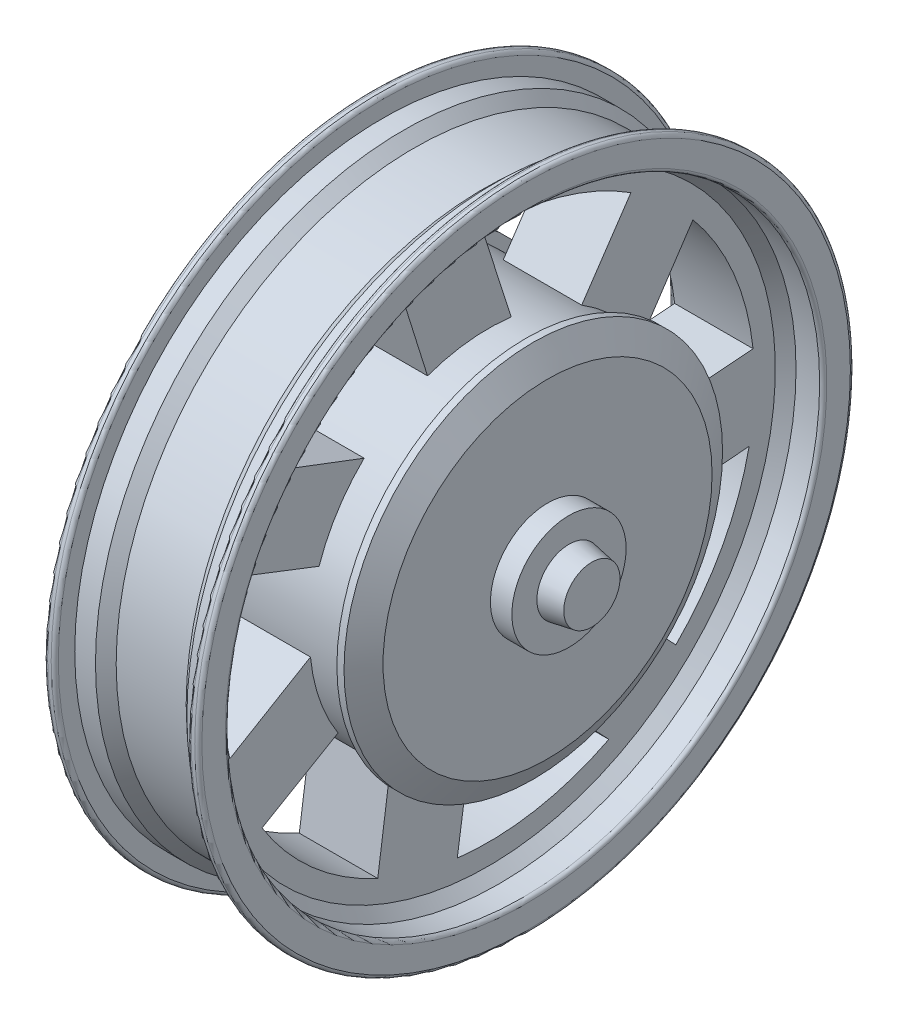
SolidWorks part; units mm, degrees
ref_plane "Front Plane" through (0, 0, 0) normal (0, 0, 1) x (1, 0, 0)
ref_plane "Top Plane" through (0, 0, 0) normal (0, 1, 0) x (1, 0, 0)
ref_plane "Right Plane" through (0, 0, 0) normal (1, 0, 0) x (0, 0, -1)
sketch "Sketch4" plane through (0, 0, 0) normal (0, 0, 1) x (1, 0, 0)
  line L0 (0, 0) -> (0, 201) construction
  line L2 (27.4562, 201) -> (34.9562, 208)
  line L3 (34.9562, 208) -> (54, 208)
  line L4 (54, 208) -> (54, 229.5)
  line L5 (54, 229.5) -> (46.5, 229.5)
  line L6 (46.5, 229.5) -> (46.5, 215.5)
  line L7 (46.5, 215.5) -> (32, 215.5)
  line L8 (32, 215.5) -> (24.5, 208.5)
  line L9 (24.5, 208.5) -> (-24.5, 208.5)
  line L10 (-54, 229.5) -> (-46.5, 229.5)
  line L11 (-54, 208) -> (-54, 229.5)
  line L12 (-46.5, 229.5) -> (-46.5, 215.5)
  line L13 (-34.9562, 208) -> (-54, 208)
  line L14 (-46.5, 215.5) -> (-32, 215.5)
  line L15 (-27.4562, 201) -> (-34.9562, 208)
  line L16 (-32, 215.5) -> (-24.5, 208.5)
  line L17 (-130.2898, 0) -> (128.111, 0) construction
  line L18 (-27.4562, 201) -> (-27.4562, 0)
  line L19 (-27.4562, 0) -> (27.4562, 0)
  line L20 (27.4562, 0) -> (27.4562, 201)
  point P23 (0, 208.5)
  dimension "D1" = 14.5
  dimension "D2" = 215.5
  dimension "D4" = 7.5
  dimension "D5" = 7.5
  dimension "D6" = 7.5
  dimension "D7" = 7.5
  dimension "D8" = 54
  dimension "D9" = 54.9124
  dimension "D10" = 229.5
revolve "Revolve1" add sketch "Sketch4" angle 360 about L17
sketch "Sketch5" plane through (27.4562, 0, 0) normal (1, 0, 0) x (0, 0, -1)
  circle A0 centre (0, 0) radius 125
  dimension "D1" = 250
extrude "Boss-Extrude2" add sketch "Sketch5" along normal up to surface (26.5438 mm away) up to face at (54, 0, 229.5)
sketch "Sketch6" plane through (-27.4562, 0, 0) normal (-1, 0, 0) x (0, 0, 1)
  circle A0 centre (0, 0) radius 125
  dimension "D1" = 250
extrude "Boss-Extrude3" add sketch "Sketch6" along normal up to surface (26.5438 mm away) up to face at (-54, 0, 208)
sketch "Sketch7" plane through (-27.4562, 0, 0) normal (-1, 0, 0) x (0, 0, 1)
  line L0 (42.4718, 117.5634) -> (60.847, 176.2949)
  line L1 (86.8778, 89.8735) -> (148.2416, 113.1666)
  line L2 (118.3955, 40.0938) -> (175.7704, 62.346)
  line L3 (124.4334, -11.8885) -> (180.9043, -45.3417)
  line L4 (105.165, -67.5672) -> (158.3351, -98.5507)
  line L5 (68.2881, -104.6983) -> (77.3424, -169.7068)
  line L6 (12.7431, -124.3488) -> (21.6703, -185.2367)
  line L7 (-39.2795, -118.6681) -> (-84.4599, -166.2792)
  line L8 (-89.2746, -87.4931) -> (-131.3127, -132.4357)
  line L9 (-117.2688, -43.2784) -> (-182.6622, -37.64)
  line L10 (-124.0667, 15.2466) -> (-185.4146, 20.0921)
  line L11 (-106.9524, 64.7008) -> (-143.3161, 119.3429)
  line L12 (-65.434, 106.5053) -> (-99.8954, 157.4902)
  line L13 (-16.0986, 123.959) -> (3.9499, 186.4582)
  circle A0 centre (0, 0) radius 125 construction
  arc A1 (86.8778, 89.8735) -> (42.4718, 117.5634) centre (0, 0) ccw
  arc A2 (148.2416, 113.1666) -> (60.847, 176.2949) centre (0, 0) ccw
  circle A3 centre (0, 0) radius 201 construction
  arc A4 (180.9043, -45.3417) -> (175.7704, 62.346) centre (0, 0) ccw
  arc A5 (124.4334, -11.8885) -> (118.3955, 40.0938) centre (0, 0) ccw
  arc A6 (77.3424, -169.7068) -> (158.3351, -98.5507) centre (0, 0) ccw
  arc A7 (68.2881, -104.6983) -> (105.165, -67.5672) centre (0, 0) ccw
  arc A8 (-84.4599, -166.2792) -> (21.6703, -185.2367) centre (0, 0) ccw
  arc A9 (-39.2795, -118.6681) -> (12.7431, -124.3488) centre (0, 0) ccw
  arc A10 (-182.6622, -37.64) -> (-131.3127, -132.4357) centre (0, 0) ccw
  arc A11 (-117.2688, -43.2784) -> (-89.2746, -87.4931) centre (0, 0) ccw
  arc A12 (-143.3161, 119.3429) -> (-185.4146, 20.0921) centre (0, 0) ccw
  arc A13 (-106.9524, 64.7008) -> (-124.0667, 15.2466) centre (0, 0) ccw
  arc A14 (3.9499, 186.4582) -> (-99.8954, 157.4902) centre (0, 0) ccw
  arc A15 (-16.0986, 123.959) -> (-65.434, 106.5053) centre (0, 0) ccw
  circle A16 centre (0, 0) radius 125 construction
  point P10 (107.3695, 85.8956)
  point P37 (0, 0)
  point P38 (95.5655, 98.8609)
  dimension "D1" = 14.5
  dimension "D2" = 7
extrude "Cut-Extrude1" cut sketch "Sketch7" against normal through all
sketch "Sketch8" plane through (54, 0, 0) normal (1, 0, 0) x (0, 0, -1)
  circle A0 centre (0, 0) radius 132.5
  dimension "D1" = 265
extrude "Boss-Extrude4" add sketch "Sketch8" along normal blind 15
sketch "Sketch9" plane through (-54, 0, 0) normal (-1, 0, 0) x (0, 0, 1)
  circle A0 centre (0, 0) radius 132.5
  dimension "D1" = 265
extrude "Boss-Extrude5" add sketch "Sketch9" along normal blind 15
chamfer "Chamfer1" distance 10 angle 60 1 edges at (69, 0, -132.5) first distance on face at (69, 0, -132.5)
chamfer "Chamfer2" distance 10 angle 60 1 edges at (-69, 0, 132.5) first distance on face at (-69, 0, 132.5)
sketch "Sketch10" plane through (69, 0, 0) normal (1, 0, 0) x (0, 0, -1)
  circle A0 centre (0, 0) radius 40
  dimension "D1" = 80
extrude "Boss-Extrude6" add sketch "Sketch10" along normal blind 15
sketch "Sketch11" plane through (-69, 0, 0) normal (-1, 0, 0) x (0, 0, 1)
  circle A0 centre (0, 0) radius 50
  dimension "D1" = 100
extrude "Boss-Extrude7" add sketch "Sketch11" along normal blind 20
sketch "Sketch12" plane through (84, 0, 0) normal (1, 0, 0) x (0, 0, -1)
  circle A0 centre (0, 0) radius 22.5
  dimension "D1" = 45
extrude "Boss-Extrude8" add sketch "Sketch12" along normal blind 16
chamfer "Chamfer3" distance 16 angle 10 1 edges at (100, 0, -22.5) first distance on face at (100, 0, -22.5)
fillet "Fillet1" radius 2.5 6 edges at (54, 0, 229.5) (-46.5, 0, 229.5) (46.5, 0, 229.5) (54, 0, 208) (-54, 0, 208) (-54, 0, 229.5)
